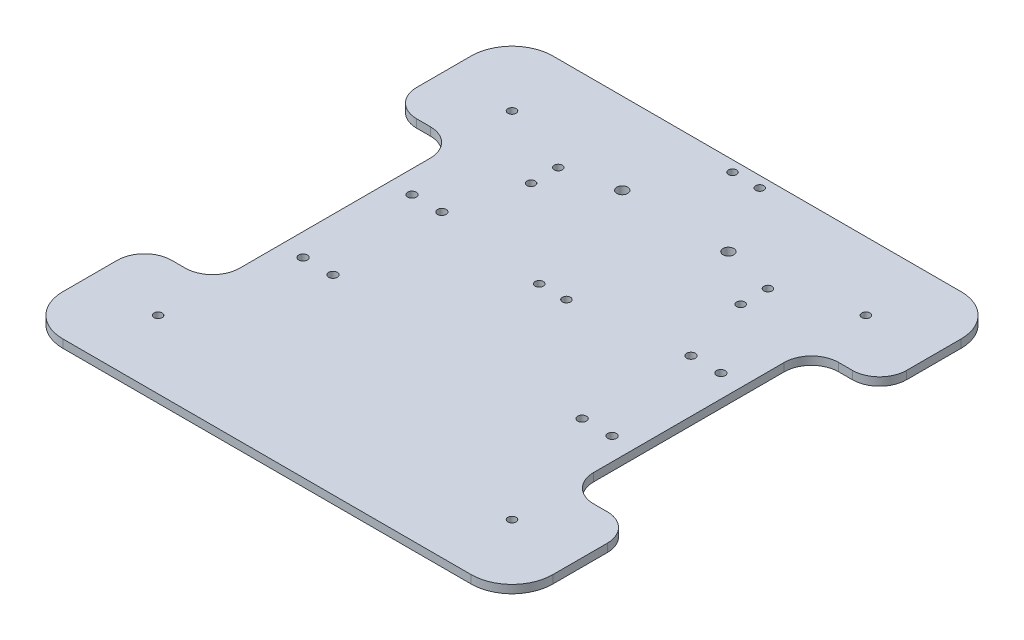
SolidWorks part; units mm, degrees
ref_plane "Спереди" through (0, 0, 0) normal (0, 0, 1) x (1, 0, 0)
ref_plane "Сверху" through (0, 0, 0) normal (0, 1, 0) x (1, 0, 0)
ref_plane "Справа" through (0, 0, 0) normal (1, 0, 0) x (0, 0, -1)
sketch "Sketch1" plane through (0, 0, 0) normal (0, 1, 0) x (1, 0, 0)
  line L1 (-90, 90) -> (90, 90)
  line L2 (-90, 90) -> (-90, -90)
  line L3 (-90, -90) -> (90, -90)
  line L4 (90, 90) -> (90, -90)
  line L5 (-90, 90) -> (90, -90) construction
  line L6 (-90, -90) -> (90, 90) construction
  point P0 (0, 0)
  dimension "D1" = 180
  dimension "D2" = 180
extrude "Boss-Extrude1" add sketch "Sketch1" along normal blind 3
fillet "Fillet1" radius 15 4 edges at (-90, 1.5, -90) (90, 1.5, -90) (-90, 1.5, 90) (90, 1.5, 90)
sketch "Sketch2" plane through (0, 3, 0) normal (0, 1, 0) x (1, 0, 0)
  line L0 (0, 0) -> (-77.5, 0) construction
  line L1 (2.75, 0) -> (-2.75, 0) construction
  line L2 (-90, 75) -> (-90, -75) construction
  line L3 (-90, 45) -> (-65, 45)
  line L4 (-90, 45) -> (-90, -45)
  line L5 (-90, -45) -> (-65, -45)
  line L6 (-65, 45) -> (-65, -45)
  line L7 (-90, 45) -> (-65, -45) construction
  line L8 (-90, -45) -> (-65, 45) construction
  line L9 (0, 0) -> (0, 45) construction
  line L10 (90, -45) -> (65, 45) construction
  line L11 (90, 45) -> (65, -45) construction
  line L12 (65, 45) -> (65, -45)
  line L13 (90, -45) -> (65, -45)
  line L14 (90, 45) -> (90, -45)
  line L15 (90, 45) -> (65, 45)
  circle A0 centre (-56.75, 20) radius 1.6
  circle A1 centre (-45.75, 20) radius 1.6
  circle A2 centre (-56.75, -20) radius 1.6
  circle A3 centre (-45.75, -20) radius 1.6
  circle A4 centre (45.75, 20) radius 1.6
  circle A5 centre (56.75, 20) radius 1.6
  circle A6 centre (45.75, -20) radius 1.6
  circle A7 centre (56.75, -20) radius 1.6
  dimension "D1" = 25
  dimension "D2" = 90
extrude "Cut-Extrude2" cut sketch "Sketch2" against normal through all
fillet "Fillet2" radius 10 8 edges at (-65, 1.5, 45) (-65, 1.5, -45) (65, 1.5, -45) (65, 1.5, 45) (90, 1.5, -45) (90, 1.5, 45) (-90, 1.5, 45) (-90, 1.5, -45)
hole_wizard "Диаметр отверстия Ø3.0 (3)1" positions "Эскиз2" profile "Эскиз1" hole size "Ø3.0" standard "Ansi Metric" end condition up to next
sketch "Эскиз2" plane through (0, 3, 0) normal (0, 1, 0) x (1, 0, 0)
  line L7 (-65, -65) -> (-65, 65) construction
  line L9 (65, 65) -> (65, -65) construction
  line L11 (-90, 65) -> (-65, 65) construction
  line L12 (-90, 75) -> (-90, 55) construction
  line L13 (-65, 65) -> (65, 65) construction
  line L14 (65, 65) -> (90, 65) construction
  line L15 (90, 55) -> (90, 75) construction
  line L17 (90, -65) -> (65, -65) construction
  line L18 (90, -75) -> (90, -55) construction
  line L19 (65, -65) -> (-65, -65) construction
  line L20 (-65, -65) -> (-90, -65) construction
  line L21 (-90, -55) -> (-90, -75) construction
  line L22 (-65, 65) -> (-65, 90) construction
  line L23 (75, 90) -> (-75, 90) construction
  point P15 (-65, -65)
  point P16 (-65, 65)
  point P19 (65, 65)
  point P20 (65, -65)
sketch "Эскиз1" plane through (-65, 3, 65) normal (1, 0, 0) x (0, 0, 1)
  line L0 (0, 0) -> (0, 3)
  line L1 (0, 3) -> (1.5, 3)
  line L2 (1.5, 3) -> (1.5, 0)
  line L5 (1.5, 0) -> (0, 0)
  line L11 (0, -6.35) -> (0, 107.95) construction
  dimension "Диаметр сквозного отверстия" = 3
  dimension "Глубина сквозного отверстия" = 3
hole_wizard "Диаметр отверстия Ø3.0 (3)2" positions "Эскиз4" profile "Эскиз3" hole size "Ø3.0" standard "Ansi Metric" end condition up to next
sketch "Эскиз4" plane through (0, 3, 0) normal (0, 1, 0) x (1, 0, 0)
  line L0 (90, 65) -> (38.5, 65) construction
  line L1 (90, 55) -> (90, 75) construction
  line L2 (38.5, 65) -> (-38.5, 65) construction
  line L3 (-38.5, 65) -> (-90, 65) construction
  line L4 (-90, 75) -> (-90, 55) construction
  line L12 (-38.5, 15) -> (-5, 15) construction
  line L13 (-5, 15) -> (5, 15) construction
  line L14 (5, 15) -> (38.5, 15) construction
  line L16 (38.5, 86) -> (5, 86) construction
  line L17 (5, 86) -> (-5, 86) construction
  line L18 (-5, 86) -> (-38.5, 86) construction
  line L20 (38.5, 15) -> (38.5, 45.5) construction
  line L21 (38.5, 45.5) -> (38.5, 55.5) construction
  line L22 (38.5, 55.5) -> (38.5, 86) construction
  line L24 (-38.5, 86) -> (-38.5, 55.5) construction
  line L25 (-38.5, 55.5) -> (-38.5, 45.5) construction
  line L26 (-38.5, 45.5) -> (-38.5, 15) construction
  line L28 (75, 90) -> (-75, 90) construction
  point P63 (-5, 15)
  point P66 (-38.5, 45.5)
  point P69 (-38.5, 55.5)
  point P72 (5, 15)
  point P75 (38.5, 45.5)
  point P78 (38.5, 55.5)
  point P81 (5, 86)
  point P84 (-5, 86)
  dimension "D1" = 10
  dimension "D2" = 71
  dimension "D3" = 77
  dimension "D4" = 4
sketch "Эскиз3" plane through (-5, 3, -15) normal (1, 0, 0) x (0, 0, 1)
  line L0 (0, 0) -> (0, 3)
  line L1 (0, 3) -> (1.5, 3)
  line L2 (1.5, 3) -> (1.5, 0)
  line L5 (1.5, 0) -> (0, 0)
  line L11 (0, -6.35) -> (0, 107.95) construction
  dimension "Диаметр сквозного отверстия" = 3
  dimension "Глубина сквозного отверстия" = 3
hole_wizard "Диаметр отверстия Ø4.0 (4)1" positions "Эскиз6" profile "Эскиз5" hole size "Ø4.0" standard "Ansi Metric" end condition up to next
sketch "Эскиз6" plane through (0, 3, 0) normal (0, 1, 0) x (1, 0, 0)
  line L0 (0, 90) -> (0, 60) construction
  line L1 (75, 90) -> (-75, 90) construction
  line L2 (0, 60) -> (0, -90) construction
  line L3 (-75, -90) -> (75, -90) construction
  line L5 (-19.5, 60) -> (19.5, 60) construction
  point P1 (-19.5, 60)
  point P20 (19.5, 60)
  dimension "D1" = 39
  dimension "D2" = 30
sketch "Эскиз5" plane through (-19.5, 3, -60) normal (1, 0, 0) x (0, 0, 1)
  line L0 (0, 0) -> (0, 3)
  line L1 (0, 3) -> (2, 3)
  line L2 (2, 3) -> (2, 0)
  line L5 (2, 0) -> (0, 0)
  line L11 (0, -6.35) -> (0, 107.95) construction
  dimension "Диаметр сквозного отверстия" = 4
  dimension "Глубина сквозного отверстия" = 3
